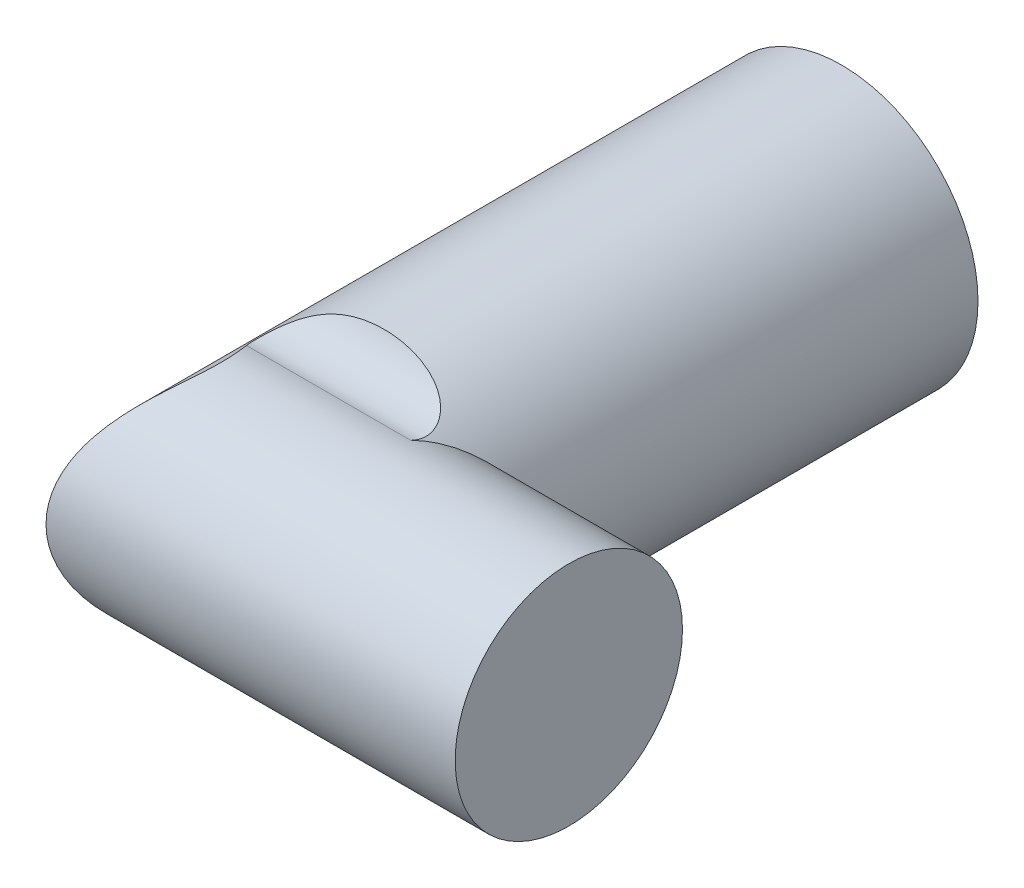
SolidWorks part; units mm, degrees
ref_plane "Plan de face" through (0, 0, 0) normal (0, 0, 1) x (1, 0, 0)
ref_plane "Plan de dessus" through (0, 0, 0) normal (0, 1, 0) x (1, 0, 0)
ref_plane "Plan de droite" through (0, 0, 0) normal (1, 0, 0) x (0, 0, -1)
sketch "Esquisse1" plane through (0, 0, 0) normal (0, 0, 1) x (1, 0, 0)
  circle A0 centre (0, 0) radius 15
  dimension "D1" = 30
extrude "Boss.-Extru.1" add sketch "Esquisse1" along normal blind 50
sketch "Esquisse2" plane through (0, 0, 0) normal (1, 0, 0) x (0, 0, -1)
  line L0 (-50, 15) -> (-50, -15) construction
  circle A0 centre (-60, 0) radius 12.5
  dimension "D1" = 25
  dimension "D2" = 10
extrude "Boss.-Extru.2" add sketch "Esquisse2" along normal blind 30 and the other way up to surface other way up to face at (15, 0, 50)
fillet "Congé1" radius 5 2 edges at (0, -7.5, 50) (0, 7.5, 50)
